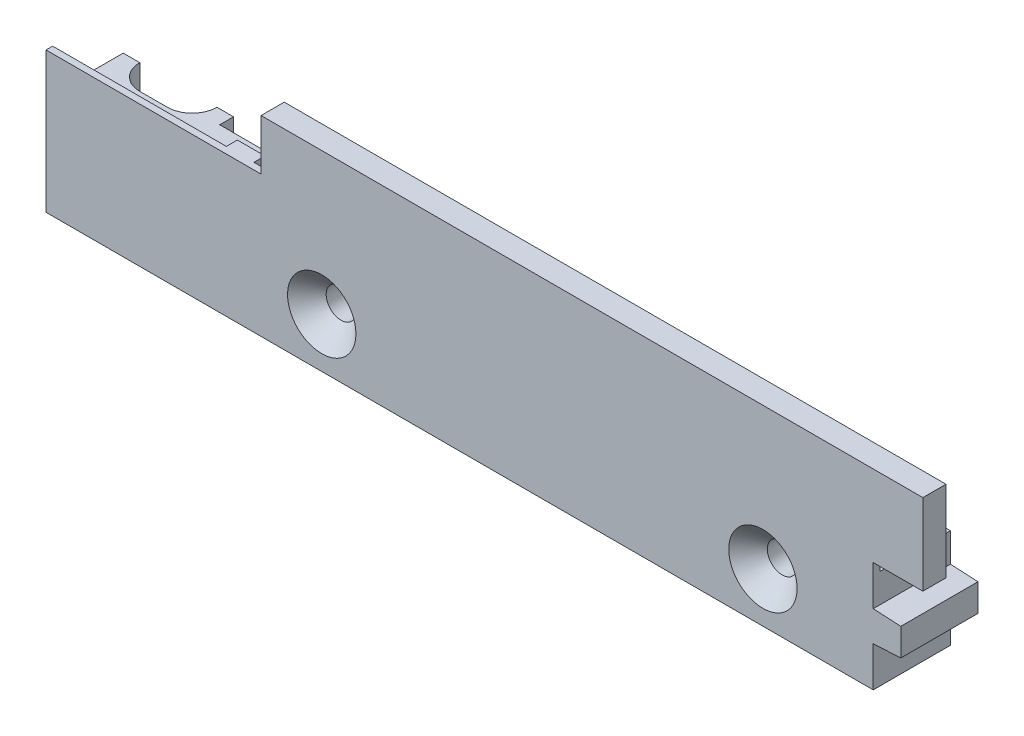
SolidWorks part; units mm, degrees
ref_plane "Front Plane" through (0, 0, 0) normal (0, 0, 1) x (1, 0, 0)
ref_plane "Top Plane" through (0, 0, 0) normal (0, 1, 0) x (1, 0, 0)
ref_plane "Right Plane" through (0, 0, 0) normal (1, 0, 0) x (0, 0, -1)
ref_axis "X-Axis" through (0, 0, 0) along (1, 0, 0)
ref_axis "Y-Axis" through (0, 42.2917, 0) along (0, -1, 0)
ref_axis "Z-Axis" through (0, 0, 55.0015) along (0, 0, -1)
sketch "Sketch1" plane through (0, 0, 0) normal (0, 0, 1) x (1, 0, 0)
  line L1 (-127.8191, -9.8629) -> (22.1809, -9.8629)
  line L2 (22.1809, -9.8629) -> (22.1809, -2.6129)
  line L3 (22.1809, -2.6129) -> (27.1809, -2.6129)
  line L4 (27.1809, -2.6129) -> (27.1809, 2.8871)
  line L5 (27.1809, 2.8871) -> (22.1809, 2.8871)
  line L6 (22.1809, 2.8871) -> (22.1809, 10.1371)
  line L7 (22.1809, 10.1371) -> (31.1809, 10.1371)
  line L8 (31.1809, 10.1371) -> (31.1809, 23.6371)
  line L10 (-127.8191, 15.6371) -> (-127.8191, -9.8629)
  line L12 (-88.8191, -25.8695) -> (-88.8191, 48.9262) construction
  line L13 (31.1809, 13.1371) -> (10.3885, 13.1371) construction
  line L14 (31.1809, 23.6371) -> (-88.8191, 23.6371) construction
  line L15 (-88.8191, 23.6371) -> (-88.8191, 15.6371)
  line L16 (-88.8191, 15.6371) -> (-127.8191, 15.6371)
  line L17 (31.1809, 23.6371) -> (31.1809, 24.8371)
  line L18 (31.1809, 24.8371) -> (-88.8191, 24.8371)
  line L19 (-88.8191, 24.8371) -> (-88.8191, 23.6371)
  point P5 (27.1809, 0.1371)
  dimension "D2" = 10
  dimension "D3" = 20
  dimension "D4" = 5.5
  dimension "D5" = 9
  dimension "D6" = 150
  dimension "D7" = 120
  dimension "D8" = 5
  dimension "D10" = 3
  dimension "D11" = 8
  dimension "D12" = 10.5
  dimension "D13" = 1.2
extrude "Boss-Extrude1" add sketch "Sketch1" along normal blind 14 and the other way blind 14
sketch "Sketch2" plane through (-127.8191, 0, 0) normal (-1, 0, 0) x (0, 0, 1)
  line L0 (-14, -9.8629) -> (14, -9.8629) construction
  line L1 (-12.8, 23.1371) -> (12.8, 23.1371) construction
  line L2 (-12.8, 23.1371) -> (-12.8, 8.1371)
  line L3 (-12.8, 8.1371) -> (12.8, 8.1371)
  line L4 (12.8, 23.1371) -> (12.8, 8.1371)
  line L5 (-14, 24.8371) -> (-14, 15.6371) construction
  line L7 (-14, 2.8871) -> (14, 2.8871) construction
  line L8 (-14, 15.6371) -> (-14, -9.8629) construction
  line L9 (14, 15.6371) -> (14, -9.8629) construction
  line L10 (0, 2.8871) -> (0, 23.1371) construction
  line L11 (-12.8, 23.1371) -> (-9.8, 23.1371)
  line L12 (-9.8, 23.1371) -> (-9.8, 24.8371)
  line L13 (-14, 24.8371) -> (14, 24.8371) construction
  line L14 (-9.8, 24.8371) -> (9.8, 24.8371)
  line L15 (9.8, 24.8371) -> (9.8, 23.1371)
  line L16 (9.8, 23.1371) -> (12.8, 23.1371)
  point P6 (0, 23.1371)
  dimension "D1" = 25.6
  dimension "D2" = 33
  dimension "D3" = 3
  dimension "D4" = 3
  dimension "D6" = 18
  dimension "D7" = 1.2
extrude "Cut-Extrude1" cut sketch "Sketch2" against normal offset from surface (157 mm away) 2 up to face at (31.1809, 17.4871, 0)
sketch "Sketch8" plane through (0, 0, 0) normal (0, 0, 1) x (1, 0, 0)
  line L0 (-127.8191, 15.6371) -> (-127.8191, -9.8629) construction
  line L1 (-107.8191, 24.8371) -> (17.1809, 24.8371)
  line L2 (-107.8191, 24.8371) -> (-107.8191, -9.8629)
  line L3 (-107.8191, -9.8629) -> (17.1809, -9.8629)
  line L4 (17.1809, 24.8371) -> (17.1809, -9.8629)
  line L5 (-127.8191, -9.8629) -> (22.1809, -9.8629) construction
  line L7 (22.1809, 2.8871) -> (22.1809, 10.1371) construction
  line L8 (29.1809, 24.8371) -> (-88.8191, 24.8371) construction
  point P12 (22.1809, 6.5121)
  dimension "D1" = 20
  dimension "D2" = 5
extrude "Cut-Extrude4" cut sketch "Sketch8" against normal blind 2.5 and the other way blind 2.5 contours L2 L3 L4 L1
sketch "Sketch9" plane through (0, 0, 0) normal (0, 0, 1) x (1, 0, 0)
  line L0 (-107.8191, -0.8629) -> (17.1809, -0.8629) construction
  line L1 (-107.8191, 8.1371) -> (-107.8191, -9.8629) construction
  line L2 (17.1809, 8.1371) -> (17.1809, -9.8629) construction
  circle A0 centre (-77.8191, -0.8629) radius 2.7
  circle A1 centre (2.1809, -0.8629) radius 2.7
  dimension "D1" = 5.4
  dimension "D2" = 80
  dimension "D3" = 15
extrude "Cut-Extrude5" cut sketch "Sketch9" against normal through all and the other way through all
chamfer "Chamfer2" distance 5 angle 3 2 edges at (27.1809, -2.6129, 0) (27.1809, 2.8871, 0) first distance on face at (24.6809, -2.6129, 0) first distance on face at (24.6809, 2.8871, 0)
sketch "Sketch14" plane through (0, 8.1371, 0) normal (0, 1, 0) x (1, 0, 0)
  line L0 (-120.3191, 4.5) -> (-115.3191, 4.5)
  line L1 (-115.3191, -4.5) -> (-120.3191, -4.5)
  line L2 (-107.8191, 0) -> (-127.8191, 0) construction
  line L3 (-107.8191, 2.5) -> (-107.8191, -2.5) construction
  line L5 (-127.8191, 12.8) -> (-127.8191, -12.8) construction
  arc A0 (-115.3191, 4.5) -> (-115.3191, -4.5) centre (-115.3191, 0) cw
  arc A1 (-120.3191, -4.5) -> (-120.3191, 4.5) centre (-120.3191, 0) cw
  point P16 (-117.8191, 0)
  dimension "D1" = 4.5
  dimension "D2" = 5
  dimension "D3" = 2.5
extrude "Cut-Extrude8" cut sketch "Sketch14" against normal blind 7
sketch "Sketch15" plane through (0, 1.1371, 0) normal (0, 1, 0) x (1, 0, 0)
  line L7 (-120.3191, -2.6) -> (-115.3191, -2.6)
  line L8 (-115.3191, 2.6) -> (-120.3191, 2.6)
  arc A2 (-120.3191, 4.5) -> (-120.3191, -4.5) centre (-120.3191, 0) ccw construction
  arc A3 (-115.3191, -4.5) -> (-115.3191, 4.5) centre (-115.3191, 0) ccw construction
  arc A6 (-120.3191, 2.6) -> (-120.3191, -2.6) centre (-120.3191, 0) ccw
  arc A7 (-115.3191, -2.6) -> (-115.3191, 2.6) centre (-115.3191, 0) ccw
  dimension "D2" = 2.6
extrude "Cut-Extrude9" cut sketch "Sketch15" against normal through all
sketch "Sketch16" plane through (0, 0, 0) normal (0, 0, 1) x (1, 0, 0)
  line L1 (-137.4451, 59.0989) -> (76.8996, 59.0989)
  line L2 (-137.4451, 59.0989) -> (-137.4451, -25.5467)
  line L3 (-137.4451, -25.5467) -> (76.8996, -25.5467)
  line L4 (76.8996, 59.0989) -> (76.8996, -25.5467)
extrude "Cut-Extrude10" cut sketch "Sketch16" against normal through all
sketch "Sketch17" plane through (0, 0, 0) normal (0, 0, -1) x (-1, 0, 0)
  line L1 (-31.1809, 24.8371) -> (-29.1809, 24.8371)
  line L2 (-31.1809, 24.8371) -> (-31.1809, 10.1371)
  line L3 (-31.1809, 10.1371) -> (-29.1809, 10.1371)
  line L4 (-29.1809, 24.8371) -> (-29.1809, 10.1371)
extrude "Cut-Extrude11" cut sketch "Sketch17" against normal up to surface (9.8 mm away) up to face at (-29.8191, 23.9871, 9.8)
sketch "Sketch18" plane through (0, 0, 0) normal (0, 0, -1) x (-1, 0, 0)
  line L0 (-27.1809, 0.1371) -> (-17.1809, 0.1371) construction
  line L1 (-27.1809, 2.6251) -> (-27.1809, -2.3509) construction
  line L2 (-17.1809, 8.1371) -> (-17.1809, -9.8629) construction
  line L3 (110.3191, -4.3629) -> (125.3191, -4.3629) construction
  line L5 (117.8191, -9.8629) -> (117.8191, 1.1371) construction
  line L9 (120.3191, 1.1371) -> (115.3191, 1.1371) construction
  line L10 (120.3191, -9.8629) -> (115.3191, -9.8629) construction
  circle A0 centre (110.3191, -4.3629) radius 1.35
  circle A1 centre (125.3191, -4.3629) radius 1.35
  circle A2 centre (-22.1809, 0.1371) radius 1.35
  point P17 (117.8191, -4.3629)
  dimension "D2" = 2.7
  dimension "D1" = 15
extrude "Cut-Extrude12" cut sketch "Sketch18" against normal blind 3
chamfer "Chamfer7" distance 3.5 angle 45 2 edges at (4.8809, -0.8629, 14) (-75.1191, -0.8629, 14)
sketch "Sketch19" plane through (0, 0, 12.8) normal (0, 0, -1) x (-1, 0, 0)
  line L0 (-22.1809, 8.1371) -> (127.8191, 8.1371) construction
  line L1 (91.3191, 15.6371) -> (96.3191, 15.6371)
  line L2 (91.3191, 15.6371) -> (91.3191, 8.1371)
  line L3 (91.3191, 8.1371) -> (96.3191, 8.1371)
  line L4 (96.3191, 15.6371) -> (96.3191, 8.1371)
  line L5 (-29.1809, 10.1371) -> (-29.1809, 23.1371) construction
  dimension "D1" = 120.5
  dimension "D2" = 5
extrude "Boss-Extrude2" add sketch "Sketch19" along normal blind 2
equation "\"Largeur Bande\"= 24.3"
equation "\"Largeur Feeder\"= \"Largeur Rail\" + 1.2 + 1.2 + 0.3"
equation "\"Largeur Rail\"= \"Largeur Bande\" + 1"
equation "\"D1@Boss-Extrude1\"=\"Largeur Feeder\"/2"
equation "\"D2@Boss-Extrude1\"=\"Largeur Feeder\"/2"
